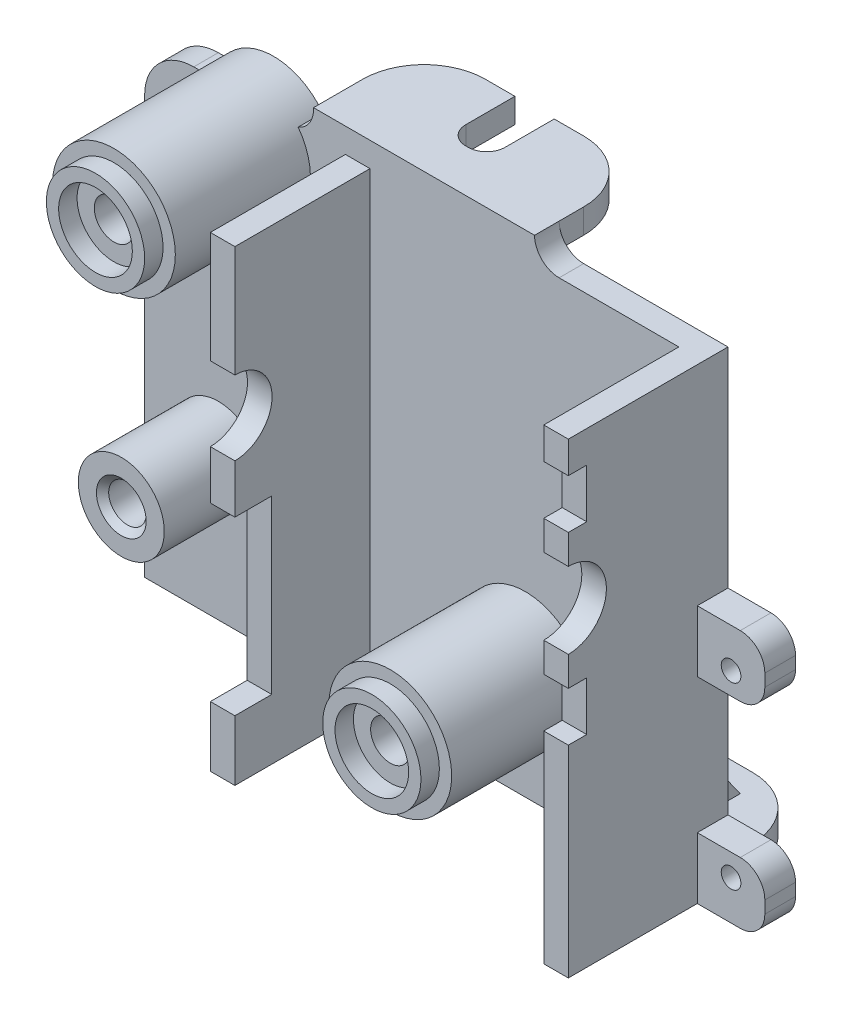
SolidWorks part; units mm, degrees
ref_plane "Face" through (0, 0, 0) normal (0, 0, 1) x (1, 0, 0)
ref_plane "Dessus" through (0, 0, 0) normal (0, 1, 0) x (1, 0, 0)
ref_plane "Droite" through (0, 0, 0) normal (1, 0, 0) x (0, 0, -1)
sketch "Esquisse30" plane through (0, 0, 0) normal (0, 0, 1) x (1, 0, 0)
  point P0 (0, -13.58)
  dimension "D1" = 13.58
ref_axis "Axe1" through (0, -13.58, -45.2896) along (0, 0, 1)
sketch "Esquisse1" plane through (0, 0, 0) normal (0, 0, 1) x (1, 0, 0)
  line L0 (-18.636, 0) -> (40.6725, 0) construction
  line L1 (0, 13.4516) -> (0, -31.9474) construction
  line L2 (-13.58, -13.58) -> (12.9107, -13.58) construction
  line L3 (11, 10.3689) -> (11, -7.2863) construction
  line L4 (12.35, 12.5556) -> (12.35, -11.4741) construction
  line L5 (37.5, 12.5556) -> (37.5, -10.7539) construction
  line L6 (-16.5535, -25.5) -> (42.4584, -25.5) construction
  line L7 (-16.0297, -27.5) -> (41.191, -27.5) construction
  line L8 (-6, 14.3889) -> (-6, -30.5277) construction
  line L9 (12.35, 10.45) -> (38.7737, 10.45) construction
  line L10 (11.7976, -10.45) -> (39.5594, -10.45) construction
  line L11 (39.5, 11.377) -> (39.5, -30.9205) construction
  line L12 (-10.1369, 12.5) -> (39.5, 12.5) construction
  line L14 (-6, 12.5) -> (39.5, 12.5)
  line L15 (-6, 12.5) -> (-6, -25.5)
  line L16 (-6, -25.5) -> (39.5, -25.5)
  line L17 (39.5, 12.5) -> (39.5, -25.5)
  circle A0 centre (0, -13.58) radius 11.5 construction
  circle A1 centre (0, -13.58) radius 1.5
extrude "Base-Extrusion" add sketch "Esquisse1" along normal mid plane 26
sketch "Esquisse5" plane through (0, 12.5, 0) normal (0, 1, 0) x (-1, 0, 0)
  line L0 (-12.35, -16.3279) -> (-12.35, 15.7701) construction
  line L1 (-10.35, -15.9222) -> (-10.35, 14.6545) construction
  line L2 (-37.5, -14.3503) -> (-37.5, 16.7842) construction
  line L3 (-39.5, -13.7925) -> (-39.5, 16.3786) construction
  line L4 (-40.8108, 11) -> (9.1448, 11) construction
  line L5 (-41.2165, -11) -> (8.3249, -11) construction
  line L7 (-37.5, 11) -> (-12.35, 11)
  line L8 (-37.5, 11) -> (-37.5, -11)
  line L9 (-37.5, -11) -> (-12.35, -11)
  line L10 (-12.35, 11) -> (-12.35, -11)
  line L11 (-10.35, 11) -> (8.7031, 11)
  line L12 (-10.35, 11) -> (-10.35, -11)
  line L13 (-10.35, -11) -> (8.7031, -11)
  line L14 (8.7031, 11) -> (8.7031, -11)
extrude "Enlèv. mat.-Extru.6" cut sketch "Esquisse5" against normal blind 40
sketch "Esquisse3" plane through (0, 0, 13) normal (0, 0, 1) x (1, 0, 0)
  circle A0 centre (0, -13.58) radius 3.5
extrude "Boss.-Extru.1" add sketch "Esquisse3" against normal blind 25
sketch "Esquisse4" plane through (0, 0, 13) normal (0, 0, 1) x (1, 0, 0)
  circle A0 centre (0, -13.58) radius 1.525
  dimension "D1" = 13.58
  dimension "D2" = 3.05
extrude "Enlèv. mat.-Extru.2" cut sketch "Esquisse4" against normal through all
sketch "Esquisse6" plane through (39.5, 0, 0) normal (1, 0, 0) x (0, 0, -1)
  line L0 (-13.8762, 0) -> (18.6073, 0) construction
  line L1 (0, 12.5) -> (0, -24.08) construction
  line L2 (11, -13.58) -> (-11, -13.58) construction
  line L3 (-13, 12.5) -> (13, 12.5) construction
  circle A0 centre (0, 0.42) radius 3.025
  dimension "D2" = 6.05
  dimension "D1" = 14
extrude "Enlèv. mat.-Extru.3" cut sketch "Esquisse6" against normal through all
sketch "Esquisse7" plane through (39.5, 0, 0) normal (1, 0, 0) x (0, 0, -1)
  circle A0 centre (0, 0.42) radius 3.1
  circle A1 centre (0, 0.42) radius 3.025 construction
  dimension "D1" = 6.2
extrude "Enlèv. mat.-Extru.4" cut sketch "Esquisse7" against normal blind 3
sketch "Esquisse8" plane through (0, -25.5, 0) normal (0, -1, 0) x (1, 0, 0)
  line L0 (-6, 21.1962) -> (-6, -20.9902) construction
  line L1 (39.5, 20.4108) -> (39.5, -20.9902) construction
  line L2 (41.0671, -20) -> (-8.3785, -20) construction
  line L3 (-7.8207, 20) -> (40.3571, 20) construction
  line L5 (-6, 20) -> (39.5, 20)
  line L6 (-6, 20) -> (-6, 11.9399)
  line L7 (-6, 11.9399) -> (39.5, 11.9399)
  line L8 (39.5, 20) -> (39.5, 11.9399)
  line L9 (-6, -20) -> (39.5, -20)
  line L10 (-6, -20) -> (-6, -11.5095)
  line L11 (-6, -11.5095) -> (39.5, -11.5095)
  line L12 (39.5, -20) -> (39.5, -11.5095)
extrude "Boss.-Extru.2" add sketch "Esquisse8" against normal blind 2
sketch "Esquisse9" plane through (0, 12.5, 0) normal (0, 1, 0) x (-1, 0, 0)
  line L0 (6.6791, -3.1) -> (-6.4741, -3.1) construction
  line L1 (7.282, 3.1) -> (-7.5154, 3.1) construction
  line L3 (6.6791, -3.1) -> (-4.7203, -3.1)
  line L4 (6.6791, -3.1) -> (6.6791, 3.1)
  line L5 (6.6791, 3.1) -> (-4.7203, 3.1)
  line L6 (-4.7203, -3.1) -> (-4.7203, 3.1)
extrude "Enlèv. mat.-Extru.5" cut sketch "Esquisse9" against normal blind 32
sketch "Esquisse12" plane through (0, 0, 0) normal (0, 0, 1) x (1, 0, 0)
  line L0 (-4.6513, 9.5) -> (15.1881, 9.5) construction
  line L1 (18.2023, -16) -> (33.4929, -16) construction
  line L2 (25, -8.6922) -> (25, -25.0789) construction
  line L3 (2.5, 14.9287) -> (2.5, -0.5811) construction
  circle A0 centre (2.5, 9.5) radius 5
  circle A1 centre (25, -16) radius 5
extrude "Boss.-Extru.3" add sketch "Esquisse12" along normal mid plane 26
sketch "Esquisse13" plane through (0, 0, 0) normal (0, 0, 1) x (1, 0, 0)
  circle A0 centre (2.5, 9.5) radius 1.6
  circle A1 centre (25, -16) radius 1.6
extrude "Enlèv. mat.-Extru.8" cut sketch "Esquisse13" against normal mid plane 32
sketch "Esquisse14" plane through (0, -23.5, 0) normal (0, 1, 0) x (-1, 0, 0)
  line L0 (8.0853, 0) -> (-43.1429, 0) construction
  line L1 (-4, -22.6142) -> (-4, -6.692) construction
  line L2 (-39.5, -22.6142) -> (-39.5, -10.961) construction
  line L3 (-16.75, -22.0374) -> (-16.75, -8.8265) construction
  line L4 (-7.2, -22.0374) -> (-7.2, -8.8265) construction
  line L5 (2.9509, -14.5) -> (-11.9906, -14.5) construction
  line L6 (-26.3, -21.5758) -> (-26.3, -16)
  line L7 (-4, -21.5758) -> (-7.2, -21.5758)
  line L8 (-4, -21.5758) -> (-4, -16)
  line L9 (-5.5, -14.5) -> (-5.7, -14.5)
  line L10 (-7.2, -21.5758) -> (-7.2, -16)
  line L11 (-28, -14.5) -> (-27.8, -14.5)
  line L12 (-29.5, -21.5758) -> (-29.5, -16)
  line L13 (-29.5, -21.5758) -> (-26.3, -21.5758)
  line L14 (-29.5, 21.5758) -> (-26.3, 21.5758)
  line L15 (-29.5, 21.5758) -> (-29.5, 16)
  line L16 (-28, 14.5) -> (-27.8, 14.5)
  line L17 (-7.2, 21.5758) -> (-7.2, 16)
  line L18 (-5.5, 14.5) -> (-5.7, 14.5)
  line L19 (-4, 21.5758) -> (-4, 16)
  line L20 (-4, 21.5758) -> (-7.2, 21.5758)
  line L21 (-26.3, 21.5758) -> (-26.3, 16)
  arc A0 (-5.5, -14.5) -> (-4, -16) centre (-5.5, -16) cw
  arc A1 (-7.2, -16) -> (-5.7, -14.5) centre (-5.7, -16) cw
  arc A2 (-26.3, -16) -> (-27.8, -14.5) centre (-27.8, -16) ccw
  arc A3 (-28, -14.5) -> (-29.5, -16) centre (-28, -16) ccw
  arc A4 (-28, 14.5) -> (-29.5, 16) centre (-28, 16) cw
  arc A5 (-26.3, 16) -> (-27.8, 14.5) centre (-27.8, 16) cw
  arc A6 (-7.2, 16) -> (-5.7, 14.5) centre (-5.7, 16) ccw
  arc A7 (-5.5, 14.5) -> (-4, 16) centre (-5.5, 16) ccw
  dimension "D1" = 1.5
extrude "Enlèv. mat.-Extru.9" cut sketch "Esquisse14" against normal through all
sketch "Esquisse15" plane through (39.5, 0, 0) normal (1, 0, 0) x (0, 0, -1)
  line L0 (-1.5, 10.2278) -> (-1.5, -10.1958) construction
  line L1 (1.5, 10.3335) -> (1.5, -9.7969) construction
  line L2 (-3.0488, 7.5) -> (3.8686, 7.5) construction
  line L3 (-5.6888, 0.42) -> (7.1769, 0.42) construction
  line L4 (-2.4473, 9.92) -> (3.3339, 9.92) construction
  line L5 (-2.4473, 5.92) -> (3.5389, 5.92) construction
  line L6 (-1.5, -5.08) -> (-1.5, -9.08)
  line L7 (1.5, 5.92) -> (-1.5, 5.92)
  line L8 (1.5, 5.92) -> (1.5, 9.92)
  line L9 (1.5, 9.92) -> (-1.5, 9.92)
  line L10 (-1.5, 5.92) -> (-1.5, 9.92)
  line L11 (1.5, -9.08) -> (-1.5, -9.08)
  line L12 (1.5, -5.08) -> (1.5, -9.08)
  line L13 (1.5, -5.08) -> (-1.5, -5.08)
extrude "Enlèv. mat.-Extru.10" cut sketch "Esquisse15" against normal blind 3
fillet "Congé1" radius 5 4 edges at (-6, -24.5, -20) (39.5, -24.5, -20) (-6, -24.5, 20) (39.5, -24.5, 20)
fillet "Congé2" radius 4 1 edges at (-6, 12.5, -12)
chamfer "Chanfrein1" distance 0.5 angle 45 4 edges at (-1.525, -13.58, -3.1) (1.525, -13.58, 3.1) (1.525, -13.58, -13) (1.525, -13.58, 13)
sketch "Esquisse16" plane through (0, 0, 0) normal (0, 0, 1) x (1, 0, 0)
  line L1 (-8.6726, 15.1395) -> (41.8545, 15.1395)
  line L2 (-8.6726, 15.1395) -> (-8.6726, -26.8516)
  line L3 (-8.6726, -26.8516) -> (41.8545, -26.8516)
  line L4 (41.8545, 15.1395) -> (41.8545, -26.8516)
extrude "Enlèv. mat.-Extru.12" cut sketch "Esquisse16" along normal blind 30
sketch "Esquisse17" plane through (0, 0, -13) normal (0, 0, -1) x (-1, 0, 0)
  line L0 (-30, -16) -> (-20.199, -16) construction
  line L1 (-25, -12.486) -> (-25, -20.8861) construction
  line L2 (-5.8684, 9) -> (2.1204, 9) construction
  line L3 (-2.5, 11.6857) -> (-2.5, 5.583) construction
  circle A0 centre (-25.0995, -16) radius 3.2
  circle A1 centre (-2.5, 9.5) radius 3.2
extrude "Enlèv. mat.-Extru.13" cut sketch "Esquisse17" against normal blind 11
sketch "Esquisse18" plane through (0, 0, 0) normal (0, 0, 1) x (1, 0, 0)
  line L0 (-4.1858, 9) -> (10.7968, 9) construction
  line L1 (2.5, 16.0119) -> (2.5, 3.4768) construction
  line L2 (18.8293, -16) -> (34.2125, -16) construction
  line L3 (25, -8.6554) -> (25, -23.4671) construction
  circle A0 centre (2.5, 9.5) radius 3
  circle A1 centre (25, -16) radius 3
  circle A2 centre (25, -16) radius 4
  circle A3 centre (2.5, 9.5) radius 4
extrude "Boss.-Extru.4" add sketch "Esquisse18" along normal blind 1.5
sketch "Esquisse20" plane through (0, 0, 0) normal (0, 0, 1) x (1, 0, 0)
  line L0 (0, -13.58) -> (19.4244, -13.58) construction
  line L1 (9.2982, -20.58) -> (14.8027, -20.58) construction
  line L2 (7.8441, -6.58) -> (16.1009, -6.58) construction
  line L4 (9.2982, -6.58) -> (13.4525, -6.58)
  line L5 (9.2982, -6.58) -> (9.2982, -20.58)
  line L6 (9.2982, -20.58) -> (13.4525, -20.58)
  line L7 (13.4525, -6.58) -> (13.4525, -20.58)
extrude "Enlèv. mat.-Extru.14" cut sketch "Esquisse20" against normal blind 3
sketch "Esquisse21" plane through (0, -23.5, 0) normal (0, 1, 0) x (-1, 0, 0)
  line L0 (-35.5, -10.467) -> (-35.5, -23.2453) construction
  line L1 (2, -12) -> (2, -22.8397) construction
  line L2 (0, -21.3691) -> (0, -12) construction
  line L3 (-33.5, -22.0283) -> (-33.5, -10.8219) construction
  line L4 (4.4712, -13) -> (-40.5065, -13) construction
  line L5 (4.0148, -18) -> (-41.0136, -18) construction
  line L7 (2, -18) -> (0, -18)
  line L8 (2, -18) -> (2, -12.6474)
  line L9 (2, -12.6474) -> (0, -12.6474)
  line L10 (0, -18) -> (0, -12.6474)
  line L11 (-33.5, -18) -> (-35.5, -18)
  line L12 (-33.5, -18) -> (-33.5, -12.6474)
  line L13 (-33.5, -12.6474) -> (-35.5, -12.6474)
  line L14 (-35.5, -18) -> (-35.5, -12.6474)
extrude "Boss.-Extru.5" add sketch "Esquisse21" along normal blind 7
chamfer "Chanfrein2" distance 7 distance2 5 2 edges at (-1, -16.5, -18) (34.5, -16.5, -18) first distance on face at (-1, -20, -18) first distance on face at (34.5, -20, -18)
sketch "Esquisse22" plane through (0, 12.5, 0) normal (0, 1, 0) x (-1, 0, 0)
  line L0 (-30.0056, -13) -> (9.2362, -13) construction
  line L1 (-30.9899, -20) -> (-6.2505, -20) construction
  line L2 (0, -11.4483) -> (0, 11.4536) construction
  line L3 (-16.75, -24.3758) -> (-16.75, -1.3426) construction
  line L4 (-25.75, -21.7509) -> (-25.75, -7.8391) construction
  line L5 (-16.65, -14.5) -> (-16.85, -14.5)
  line L6 (-27.512, -11) -> (-7.563, -11) construction
  line L7 (-18.35, -16) -> (-18.35, -20)
  line L8 (-18.35, -20) -> (-25.75, -20)
  line L9 (-25.75, -20) -> (-25.75, -11)
  line L10 (-18.35, -21.1603) -> (-18.35, -14.0154) construction
  line L11 (-28, -14.5) -> (-14.5154, -14.5) construction
  line L12 (-25.75, -11) -> (-7.75, -11)
  line L13 (-7.75, -20) -> (-7.75, -11)
  line L14 (-15.15, -20) -> (-7.75, -20)
  line L15 (-15.15, -16) -> (-15.15, -20)
  arc A0 (-18.35, -16) -> (-16.85, -14.5) centre (-16.85, -16) cw
  arc A1 (-15.15, -16) -> (-16.65, -14.5) centre (-16.65, -16) ccw
  point P17 (-16.75, -13)
  point P18 (-16.75, -20)
  point P26 (-16.75, -14.5)
  point P31 (-16.75, -11)
  point P33 (-16.75, -14.5)
  dimension "D1" = 1.5
extrude "Boss.-Extru.6" add sketch "Esquisse22" along normal blind 2
fillet "Congé3" radius 2 2 edges at (25.75, 12.5, -12) (7.75, 12.5, -12)
fillet "Congé4" radius 5 2 edges at (25.75, 13.5, -20) (7.75, 13.5, -20)
sketch "Esquisse23" plane through (0, 0, -13) normal (0, 0, -1) x (-1, 0, 0)
  text T0 "www.a4.fr" font "Arial" height 3.5
extrude "Boss.-Extru.7" add sketch "Esquisse23" along normal blind 0.3
sketch "Esquisse25" plane through (0, 0, -13) normal (0, 0, -1) x (-1, 0, 0)
  line L0 (-36.9245, -20.5) -> (-51.2569, -20.5) construction
  line L1 (-35.9898, -25.5) -> (-53.9573, -25.5) construction
  line L2 (-47.3622, -9.5) -> (-9.5, -9.5) construction
  line L3 (-47.3622, -4.5) -> (-36.9245, -4.5) construction
  line L4 (-39.469, 2.4971) -> (-39.469, -30.2183) construction
  line L5 (-45, 0.9911) -> (-45, -27.7776) construction
  line L6 (-42.25, -2.9035) -> (-42.25, -27.0506) construction
  line L7 (-43.5195, -7.7) -> (-41.3385, -7.7) construction
  line L8 (-42.9483, -22.3) -> (-41.3385, -22.3) construction
  line L10 (-45, -4.5) -> (-39.0536, -4.5)
  line L11 (-45, -4.5) -> (-45, -9.5)
  line L12 (-45, -9.5) -> (-39.0536, -9.5)
  line L13 (-39.0536, -4.5) -> (-39.0536, -9.5)
  line L14 (-45, -20.5) -> (-39.1574, -20.5)
  line L15 (-45, -20.5) -> (-45, -25.5)
  line L16 (-45, -25.5) -> (-39.1574, -25.5)
  line L17 (-39.1574, -20.5) -> (-39.1574, -25.5)
  circle A0 centre (-42.25, -7.7) radius 0.8
  circle A1 centre (-42.25, -22.3) radius 0.8
extrude "Boss.-Extru.8" add sketch "Esquisse25" against normal blind 2.5
fillet "Congé5" radius 2 4 edges at (45, -9.5, -11.75) (45, -4.5, -11.75) (45, -20.5, -11.75) (45, -25.5, -11.75)
sketch "Esquisse26" [suppressed] plane through (0, 0, -3.1) normal (0, 0, 1) x (1, 0, 0)
  circle A1 centre (0, -13.58) radius 3.5
  circle A2 centre (0, -13.58) radius 3.5
  dimension "D1" = 0
extrude "Enlèv. mat.-Extru.15" [suppressed] cut sketch "Esquisse26" against normal up to surface (7.9 mm away) up to face at (20, -16, -11)
sketch "Esquisse27" [suppressed] plane through (0, 0, -11) normal (0, 0, 1) x (1, 0, 0)
  circle A0 centre (0, -13.58) radius 3.95
  dimension "D1" = 7.9
extrude "Enlèv. mat.-Extru.16" [suppressed] cut sketch "Esquisse27" against normal blind 1
sketch "Esquisse28" [suppressed] plane through (0, 0, -12) normal (0, 0, 1) x (1, 0, 0)
  circle A0 centre (0, -13.58) radius 2.5
  dimension "D1" = 5
extrude "Enlèv. mat.-Extru.17" [suppressed] cut sketch "Esquisse28" against normal up to next
sketch "Esquisse29" [suppressed] plane through (0, 0, -11) normal (0, 0, 1) x (1, 0, 0)
  line L0 (-6, -25.5) -> (-6, 8.5) construction
  circle A0 centre (0, -13.58) radius 6
  circle A2 centre (0, -13.58) radius 5
  circle A3 centre (0, -13.58) radius 3.95 construction
  dimension "D2" = 10
extrude "Boss.-Extru.9" [suppressed] add sketch "Esquisse29" along normal blind 4
equation "\"D1@Esquisse6\" = 14"
